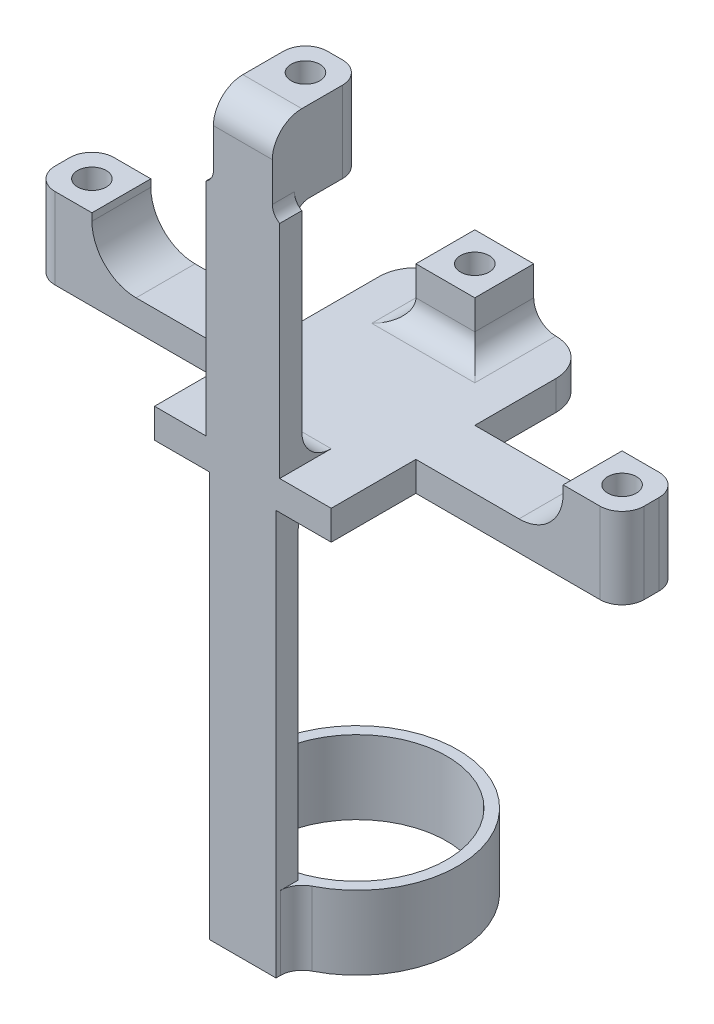
SolidWorks part; units mm, degrees
ref_plane "正面" through (0, 0, 0) normal (0, 0, 1) x (1, 0, 0)
ref_plane "平面" through (0, 0, 0) normal (0, 1, 0) x (1, 0, 0)
ref_plane "右側面" through (0, 0, 0) normal (1, 0, 0) x (0, 0, -1)
sketch "ｽｹｯﾁ1" plane through (0, 0, 0) normal (0, 1, 0) x (1, 0, 0)
  circle A0 centre (0, 0) radius 12.2
  circle A1 centre (0, 0) radius 13.7
ref_plane "平面1" through (0, 10, 0) normal (0, 1, 0) x (1, 0, 0)
extrude "ﾎﾞｽ - 押し出し1" add sketch "ｽｹｯﾁ1" along normal up to surface (10 mm away) up to plane "平面1"
ref_plane "平面2" through (0, 0, 12.5) normal (0, 0, 1) x (1, 0, 0)
sketch "ｽｹｯﾁ3" plane through (0, 0, 12.5) normal (0, 0, 1) x (1, 0, 0)
  line L0 (-13.7, 0) -> (13.7, 0) construction
  line L1 (-4.5, 0) -> (4.5, 0)
  line L2 (-4.5, 0) -> (-4.5, 55)
  line L3 (-4.5, 55) -> (4.5, 55)
  line L4 (4.5, 0) -> (4.5, 55)
extrude "ﾎﾞｽ - 押し出し2" add sketch "ｽｹｯﾁ3" along normal blind 3
ref_plane "平面3" through (0, 55, 0) normal (0, 1, 0) x (1, 0, 0)
ref_plane "平面4" through (0, 59, 0) normal (0, 1, 0) x (1, 0, 0)
sketch "ｽｹｯﾁ4" plane through (0, 55, 0) normal (0, 1, 0) x (1, 0, 0)
  line L1 (-12, -15.5) -> (12, -15.5)
  line L2 (-12, -15.5) -> (-12, 20)
  line L3 (-12, 20) -> (12, 20)
  line L4 (12, -15.5) -> (12, 20)
  point P4 (0, 0)
extrude "ﾎﾞｽ - 押し出し3" add sketch "ｽｹｯﾁ4" along normal up to surface (4 mm away) up to plane "平面4"
fillet "ﾌｨﾚｯﾄ1" radius 4 1 edges at (0, 55, 12.5)
sketch "ｽｹｯﾁ5" plane through (0, 55, 0) normal (0, 1, 0) x (1, 0, 0)
  line L1 (0, 4) -> (-40, 4)
  line L2 (0, 4) -> (0, -4)
  line L3 (0, -4) -> (-40, -4)
  line L4 (-40, 4) -> (-40, -4)
extrude "ﾎﾞｽ - 押し出し4" add sketch "ｽｹｯﾁ5" along normal up to surface (4 mm away) up to plane "平面4"
sketch "ｽｹｯﾁ6" plane through (0, 55, 0) normal (0, 1, 0) x (1, 0, 0)
  line L0 (-40, -4) -> (-12, -4) construction
  line L1 (-40, 4) -> (-32, 4)
  line L2 (-40, 4) -> (-40, -4)
  line L3 (-40, -4) -> (-32, -4)
  line L4 (-32, 4) -> (-32, -4)
extrude "ﾎﾞｽ - 押し出し5" add sketch "ｽｹｯﾁ6" along normal blind 11
fillet "ﾌｨﾚｯﾄ2" radius 6 1 edges at (-32, 59, 0)
hole_wizard "#0 すきま穴1" positions "ｽｹｯﾁ9" profile "ｽｹｯﾁ10" hole size "#0" standard "Ansi Inch" end condition through all
sketch "ｽｹｯﾁ9" plane through (0, 66, 0) normal (0, 1, 0) x (1, 0, 0)
  point P0 (-36, 0)
  point P3 (0, 0)
sketch "ｽｹｯﾁ10" plane through (-36, 66, 0) normal (1, 0, 0) x (0, 0, 1)
  line L0 (0, 0) -> (0, 66)
  line L1 (0, 66) -> (1.95, 66)
  line L2 (1.95, 66) -> (1.95, 0)
  line L5 (1.95, 0) -> (0, 0)
  line L11 (0, -6.35) -> (0, 107.95) construction
  dimension "通し穴の直径" = 3.9
  dimension "通し穴の深さ" = 66
mirror "ﾐﾗｰ1" about plane through (0, 0, 0) normal (1, 0, 0) of "#0 すきま穴1", "ﾌｨﾚｯﾄ2", "ﾎﾞｽ - 押し出し5", "ﾎﾞｽ - 押し出し4"
sketch "ｽｹｯﾁ11" plane through (0, 55, 0) normal (0, 1, 0) x (1, 0, 0)
  line L1 (4, 12) -> (-4, 12)
  line L2 (4, 12) -> (4, 20)
  line L3 (4, 20) -> (-4, 20)
  line L4 (-4, 12) -> (-4, 20)
  point P4 (0, 0)
  point P5 (0, 0)
extrude "ﾎﾞｽ - 押し出し6" add sketch "ｽｹｯﾁ11" along normal blind 11
hole_wizard "#0 すきま穴2" positions "ｽｹｯﾁ12" profile "ｽｹｯﾁ13" hole size "#0" standard "Ansi Inch" end condition up to next
sketch "ｽｹｯﾁ12" plane through (0, 66, 0) normal (0, 1, 0) x (1, 0, 0)
  point P0 (0, 16)
  point P4 (0, 0)
sketch "ｽｹｯﾁ13" plane through (0, 66, -16) normal (1, 0, 0) x (0, 0, 1)
  line L0 (0, 0) -> (0, 11)
  line L1 (0, 11) -> (1.95, 11)
  line L2 (1.95, 11) -> (1.95, 0)
  line L5 (1.95, 0) -> (0, 0)
  line L11 (0, -6.35) -> (0, 107.95) construction
  dimension "通し穴の直径" = 3.9
  dimension "通し穴の深さ" = 11
fillet "ﾌｨﾚｯﾄ3" radius 3 1 edges at (0, 59, -12)
fillet "ﾌｨﾚｯﾄ4" radius 3 1 edges at (-4, 59, -14.5)
fillet "ﾌｨﾚｯﾄ5" radius 3 1 edges at (4, 59, -14.5)
sketch "ｽｹｯﾁ14" plane through (0, 59, 0) normal (0, 1, 0) x (1, 0, 0)
  line L0 (-12, -15.5) -> (12, -15.5) construction
  line L1 (5, -15.5) -> (-5, -15.5)
  line L2 (5, -15.5) -> (5, -12.5)
  line L3 (5, -12.5) -> (-5, -12.5)
  line L4 (-5, -15.5) -> (-5, -12.5)
  point P6 (0, 0)
  point P7 (0, 0)
  point P8 (0, 0)
  point P9 (0, 0)
  point P10 (0, 0)
ref_plane "平面5" through (0, 89, 0) normal (0, 1, 0) x (1, 0, 0)
extrude "ﾎﾞｽ - 押し出し7" add sketch "ｽｹｯﾁ14" along normal up to surface (30 mm away) up to plane "平面5"
fillet "ﾌｨﾚｯﾄ6" radius 4 1 edges at (0, 59, 12.5)
ref_plane "平面6" through (0, 89, 0) normal (0, 1, 0) x (1, 0, 0)
sketch "ｽｹｯﾁ16" plane through (0, 89, 0) normal (0, 1, 0) x (1, 0, 0)
  line L0 (-5, -15.5) -> (5, -15.5) construction
  line L1 (-4, -15.5) -> (4, -15.5)
  line L2 (-4, -15.5) -> (-4, -3)
  line L3 (-4, -3) -> (4, -3)
  line L4 (4, -15.5) -> (4, -3)
extrude "ﾎﾞｽ - 押し出し8" add sketch "ｽｹｯﾁ16" along normal blind 11
fillet "ﾌｨﾚｯﾄ7" radius 4 1 edges at (0, 100, 15.5)
fillet "ﾌｨﾚｯﾄ8" radius 2 1 edges at (0, 89, 12.5)
fillet "ﾌｨﾚｯﾄ9" radius 2 1 edges at (4, 89, 14)
fillet "ﾌｨﾚｯﾄ10" radius 2 1 edges at (-4, 89, 14)
hole_wizard "#0 すきま穴3" positions "ｽｹｯﾁ17" profile "ｽｹｯﾁ18" hole size "#0" standard "Ansi Inch" end condition up to next
sketch "ｽｹｯﾁ17" plane through (0, 100, 0) normal (0, 1, 0) x (1, 0, 0)
  point P0 (0, -7)
  point P3 (0, 0)
sketch "ｽｹｯﾁ18" plane through (0, 100, 7) normal (1, 0, 0) x (0, 0, 1)
  line L0 (0, 0) -> (0, 11)
  line L1 (0, 11) -> (1.95, 11)
  line L2 (1.95, 11) -> (1.95, 0)
  line L5 (1.95, 0) -> (0, 0)
  line L11 (0, -6.35) -> (0, 107.95) construction
  dimension "通し穴の直径" = 3.9
  dimension "通し穴の深さ" = 11
fillet "ﾌｨﾚｯﾄ11" radius 5 1 edges at (12, 57, -20)
fillet "ﾌｨﾚｯﾄ12" radius 5 1 edges at (-12, 57, -20)
fillet "ﾌｨﾚｯﾄ13" radius 3 1 edges at (-40, 60.5, -4)
fillet "ﾌｨﾚｯﾄ14" radius 3 1 edges at (-40, 60.5, 4)
fillet "ﾌｨﾚｯﾄ15" radius 3 1 edges at (40, 60.5, -4)
fillet "ﾌｨﾚｯﾄ16" radius 3 1 edges at (40, 60.5, 4)
fillet "ﾌｨﾚｯﾄ17" radius 3 1 edges at (4, 94.5, 3)
fillet "ﾌｨﾚｯﾄ18" radius 3 1 edges at (-4, 94.5, 3)
fillet "ﾌｨﾚｯﾄ19" radius 3 1 edges at (4.5, 5, 12.9399)
fillet "ﾌｨﾚｯﾄ20" radius 3 1 edges at (-4.5, 5, 12.9399)
